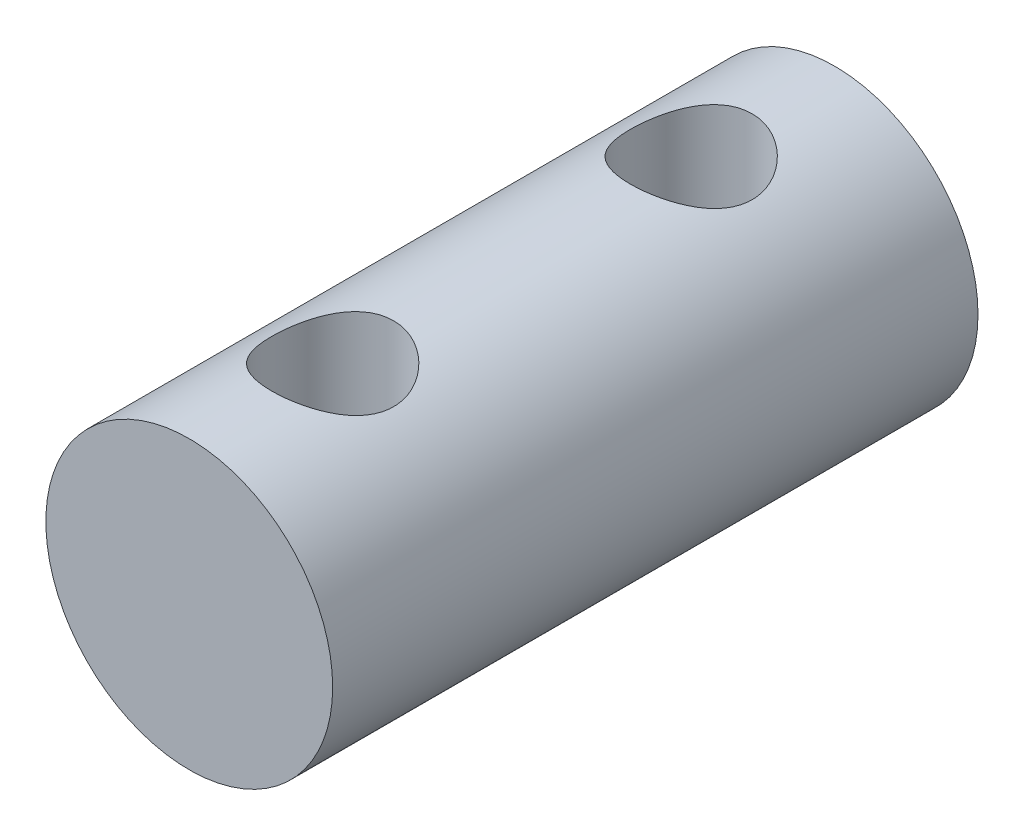
SolidWorks part; units mm, degrees
ref_plane "前视基准面" through (0, 0, 0) normal (0, 0, 1) x (1, 0, 0)
ref_plane "上视基准面" through (0, 0, 0) normal (0, 1, 0) x (1, 0, 0)
ref_plane "右视基准面" through (0, 0, 0) normal (1, 0, 0) x (0, 0, -1)
sketch "草图1" plane through (0, 0, 0) normal (0, 0, 1) x (1, 0, 0)
  circle A0 centre (0, 0) radius 4
  dimension "D1" = 8
extrude "拉伸1" add sketch "草图1" along normal blind 18
sketch "草图2" plane through (0, 0, 0) normal (0, 1, 0) x (1, 0, 0)
  line L0 (0, -1000) -> (0, 49000) construction
  line L1 (4, 0) -> (-4, 0) construction
  line L2 (-4, -18) -> (4, -18) construction
  circle A0 centre (0, -4) radius 1.7
  circle A1 centre (0, -14) radius 1.7
  dimension "D3" = 3.4
  dimension "D4" = 3.4
  dimension "D1" = 4
  dimension "D2" = 4
extrude "切除-拉伸1" cut sketch "草图2" against normal blind 10 and the other way blind 10
